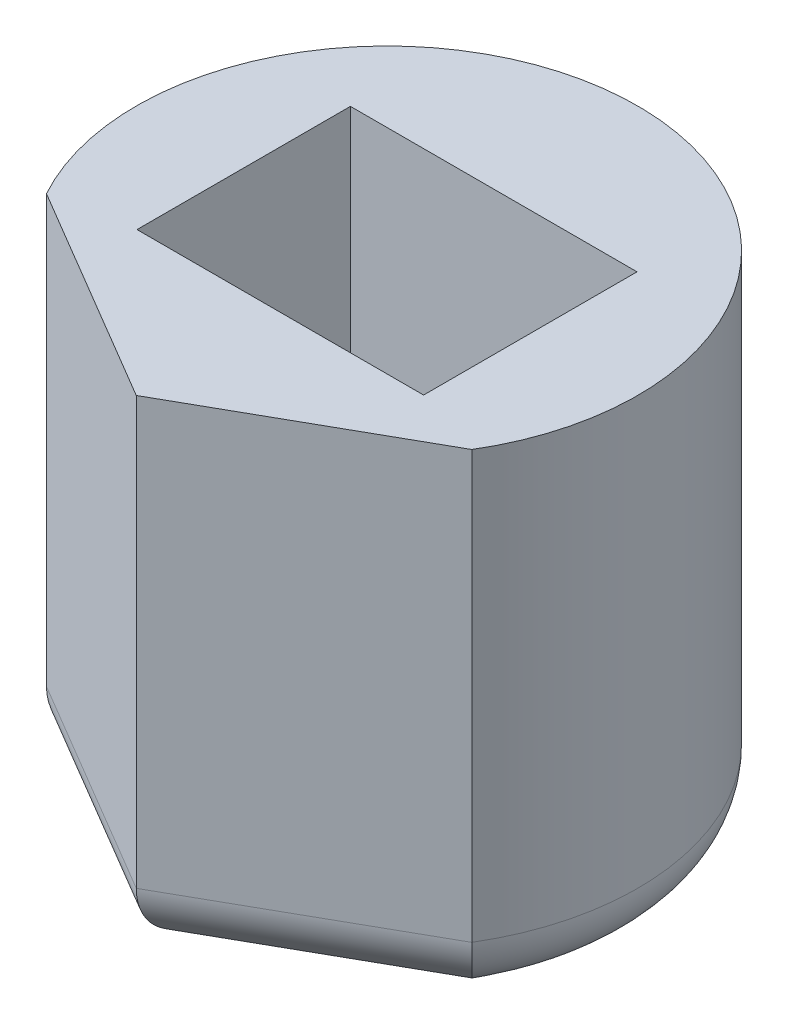
SolidWorks part; units mm, degrees
ref_plane "Front Plane" through (0, 0, 0) normal (0, 0, 1) x (1, 0, 0)
ref_plane "Top Plane" through (0, 0, 0) normal (0, 1, 0) x (1, 0, 0)
ref_plane "Right Plane" through (0, 0, 0) normal (1, 0, 0) x (0, 0, -1)
sketch "Sketch1" plane through (0, 0, 0) normal (0, 1, 0) x (1, 0, 0)
  line L1 (-2.35, 1.75) -> (2.35, 1.75)
  line L2 (-2.35, 1.75) -> (-2.35, -1.75)
  line L3 (-2.35, -1.75) -> (2.35, -1.75)
  line L4 (2.35, 1.75) -> (2.35, -1.75)
  line L5 (-2.35, 1.75) -> (2.35, -1.75) construction
  line L6 (-2.35, -1.75) -> (2.35, 1.75) construction
  circle A0 centre (0, 0) radius 4.1118
  dimension "D1" = 3.5
  dimension "D2" = 4.7
extrude "Boss-Extrude1" add sketch "Sketch1" along normal blind 6
sketch "Sketch3" plane through (0, 6, 0) normal (0, 1, 0) x (1, 0, 0)
  line L0 (0, -4.1118) -> (-6.9569, 0)
  line L1 (0, -4.1118) -> (6.0147, -0.7206)
  line L2 (-6.9569, 0) -> (0.8211, -8.5035)
  line L3 (0.8211, -8.5035) -> (6.0147, -0.7206)
  circle A0 centre (0, 0) radius 4.1118 construction
  dimension "D1" = 120
extrude "Cut-Extrude1" cut sketch "Sketch3" against normal blind 6
sketch "Sketch4" plane through (0, 0, 0) normal (0, -1, 0) x (1, 0, 0)
  line L0 (-3.6022, 1.9828) -> (0, 4.1118)
  line L1 (0, 4.1118) -> (3.5182, 2.1282)
  line L4 (3.5182, 2.1282) -> (0, 4.1118)
  line L5 (0, 4.1118) -> (-3.6022, 1.9828)
  line L6 (3.5182, 2.1282) -> (0, 4.1118)
  line L7 (0, 4.1118) -> (-3.6022, 1.9828)
  arc A0 (3.5182, 2.1282) -> (0.4946, -4.082) centre (0, 0) cw
  arc A1 (-3.6022, 1.9828) -> (3.5182, 2.1282) centre (0, 0) ccw construction
  arc A3 (-3.6022, 1.9828) -> (3.5182, 2.1282) centre (0, 0) ccw
  arc A4 (0.4946, -4.082) -> (3.5182, 2.1282) centre (0, 0) ccw
  arc M4 (-3.6022, 1.9828) -> (3.5182, 2.1282) centre (0, 0) ccw
  line M5 (3.5182, 2.1282) -> (0, 4.1118)
  line M6 (0, 4.1118) -> (-3.6022, 1.9828)
  line M7 (2.35, 1.75) -> (2.35, -1.75)
  line M8 (2.35, -1.75) -> (-2.35, -1.75)
  line M9 (-2.35, -1.75) -> (-2.35, 1.75)
  line M10 (-2.35, 1.75) -> (2.35, 1.75)
  dimension "D1" = 0
extrude "Boss-Extrude2" add sketch "Sketch4" along normal blind 2 contours M6 M4 M5 M10 M7 M8 M9 region at (-1.7419, 0, 2.9472)
fillet "Fillet1" radius 1 3 edges at (0.0839, -2, -4.111) (-1.8011, -2, 3.0473) (1.7591, -2, 3.12)
sketch "Sketch5" plane through (0, -2, 0) normal (0, -1, 0) x (1, 0, 0)
  line L1 (-2.35, 1.75) -> (2.35, 1.75)
  line L2 (-2.35, 1.75) -> (-2.35, -1.75)
  line L3 (-2.35, -1.75) -> (2.35, -1.75)
  line L4 (2.35, 1.75) -> (2.35, -1.75)
extrude "Boss-Extrude3" add sketch "Sketch5" against normal blind 2
